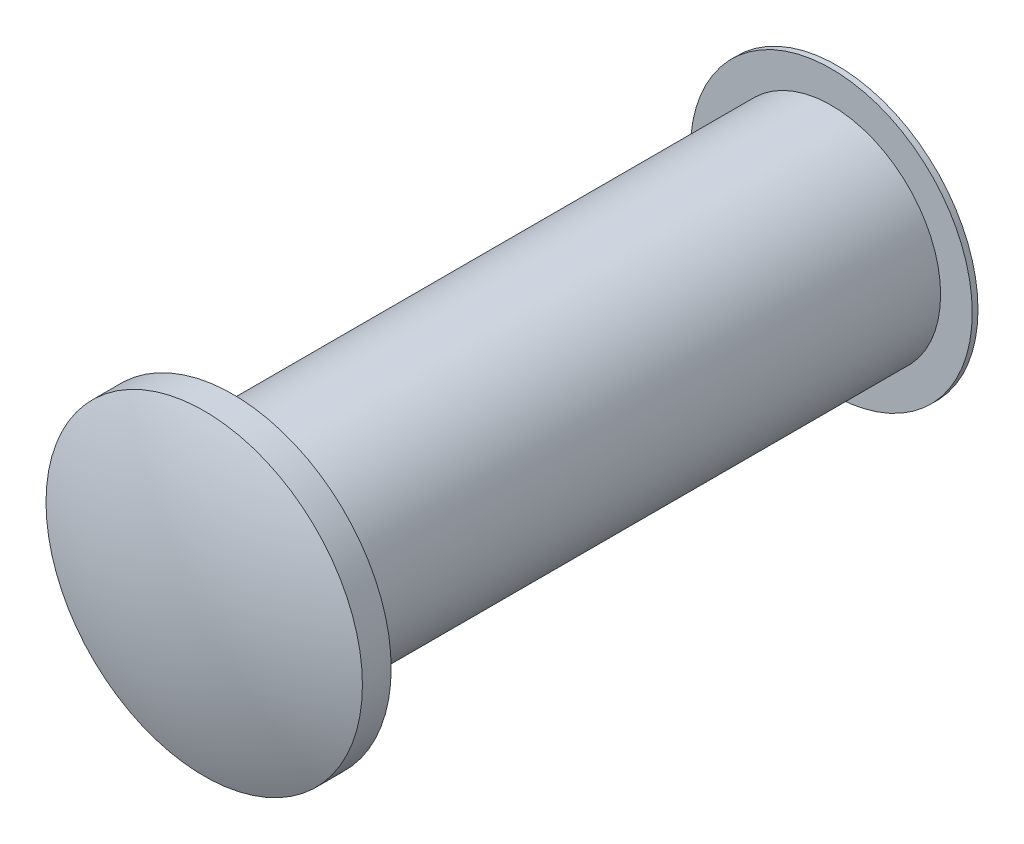
SolidWorks part; units mm, degrees
material "AISI 316 Stainless Steel Sheet (SS)"
ref_plane "Front Plane" through (0, 0, 0) normal (0, 0, 1) x (1, 0, 0)
ref_plane "Top Plane" through (0, 0, 0) normal (0, 1, 0) x (1, 0, 0)
ref_plane "Right Plane" through (0, 0, 0) normal (1, 0, 0) x (0, 0, -1)
sketch "Sketch1" plane through (0, 0, 0) normal (0, 0, 1) x (1, 0, 0)
  circle A0 centre (0, 0) radius 0.9652
  dimension "D1" = 1.9304
extrude "Boss-Extrude1" add sketch "Sketch1" along normal blind 5.2832 contours A0
sketch "Sketch2" plane through (0, 0, 5.2832) normal (0, 0, 1) x (1, 0, 0)
  circle A0 centre (0, 0) radius 1.397
  dimension "D1" = 2.794
extrude "Boss-Extrude2" add sketch "Sketch2" along normal blind 0.254
dome "Dome1" faces to dome 1 distance 0.2794 reverse direction no elliptical dome no face at (1.397, 0, 5.5372) parameters "D1"=0.2794
sketch "Sketch3" plane through (0, 0, 0) normal (0, 0, -1) x (-1, 0, 0)
  circle A0 centre (0, 0) radius 1.2446
  dimension "D1" = 2.4892
extrude "Boss-Extrude3" add sketch "Sketch3" along normal blind 0.0508
sketch "Sketch4" plane through (0, 0, -0.0508) normal (0, 0, -1) x (-1, 0, 0)
  circle A0 centre (0, 0) radius 0.5921
extrude "Cut-Extrude1" cut sketch "Sketch4" against normal blind 0.508
